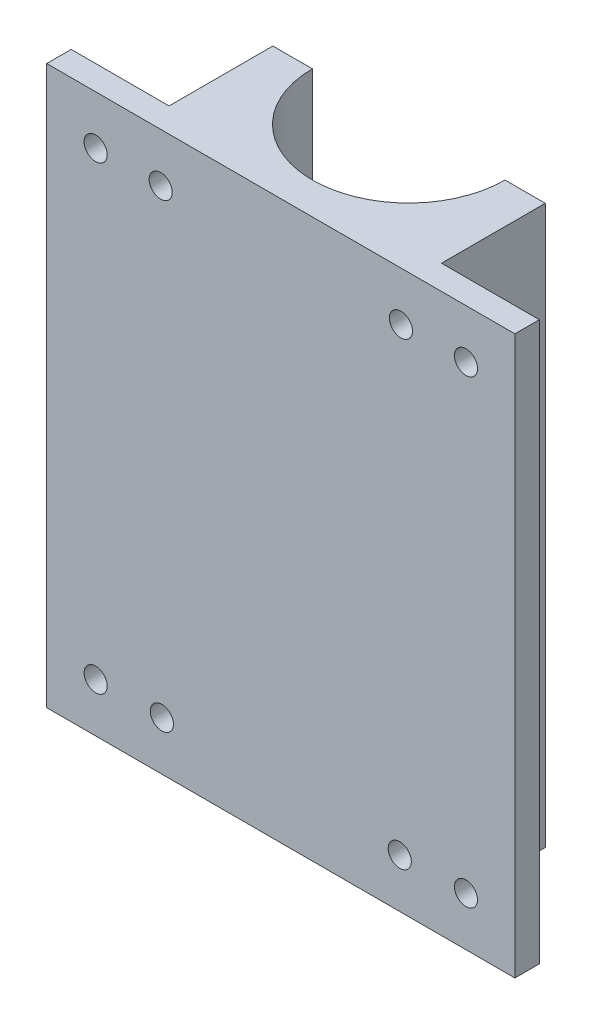
SolidWorks part; units mm, degrees
ref_plane "Front Plane" through (0, 0, 0) normal (0, 0, 1) x (1, 0, 0)
ref_plane "Top Plane" through (0, 0, 0) normal (0, 1, 0) x (1, 0, 0)
ref_plane "Right Plane" through (0, 0, 0) normal (1, 0, 0) x (0, 0, -1)
sketch "Sketch1" plane through (0, 0, 0) normal (0, 1, 0) x (1, 0, 0)
  line L1 (-23.8485, 17.6982) -> (36.9033, 17.6982)
  line L2 (-23.8485, 17.6982) -> (-23.8485, 14.5232)
  line L3 (-23.8485, 14.5232) -> (36.9033, 14.5232)
  line L4 (36.9033, 17.6982) -> (36.9033, 14.5232)
  line L6 (24.2033, 31.1659) -> (-11.1467, 31.1659)
  line L7 (24.2033, 31.1659) -> (24.2033, 17.6982)
  line L8 (24.2033, 17.6982) -> (-11.1467, 17.6982)
  line L9 (-11.1467, 31.1659) -> (-11.1467, 17.6982)
  line L10 (-6.0203, 31.1659) -> (-5.7203, 31.1659)
  line L11 (18.9797, 31.1659) -> (18.6797, 31.1659)
  line L12 (6.5283, 38.6577) -> (6.5283, -0.813) construction
  arc A2 (-6.0203, 31.1659) -> (18.9797, 31.1659) centre (6.4797, 31.1659) ccw
  arc A3 (-5.7203, 31.1659) -> (18.6797, 31.1659) centre (6.4797, 31.1659) ccw
  dimension "D1" = 12.7018
  dimension "D2" = 12.7
extrude "Boss-Extrude3" add sketch "Sketch1" along normal blind 72.39 contours A2 L6 L9 L1 | L12 A2 L1 L2 L3 | L1 L12 L3 L4 | A2 L1 L7 L6 region at (6.5274, 0, -16.1107) region at (-10.7684, 0, -24.432)
extrude "Boss-Extrude4" add sketch "Sketch1<13>" along normal blind 51.39 contours A2 L11 A3 L10
sketch "Sketch1<13>" plane through (0, 0, 0) normal (0, 1, 0) x (1, 0, 0) same geometry as "Sketch1"
hole_wizard "Ø3.0mm Dowel Hole1" positions "Sketch4" profile "Sketch5" hole size "Ø3.0" standard "ANSI Metric" end condition through all
sketch "Sketch4" plane through (0, 0, -17.6982) normal (0, 0, -1) x (-1, 0, 0)
  line L0 (-24.2033, 72.39) -> (-36.9033, 72.39) construction
  line L1 (-36.9033, 72.39) -> (-36.9033, 0) construction
  line L3 (-24.2033, 0) -> (-36.9033, 0) construction
  point P0 (-30.5533, 66.04)
  point P9 (-30.5533, 6.35)
  point P20 (-30.5533, 0)
  dimension "D1" = 6.35
  dimension "D2" = 6.35
  dimension "D3" = 6.35
  dimension "D4" = 6.35
sketch "Sketch5" plane through (30.5533, 66.04, -17.6982) normal (1, 0, 0) x (0, 1, 0)
  line L0 (0, 0) -> (0, 3.175)
  line L1 (0, 3.175) -> (1.5, 3.175)
  line L2 (1.5, 3.175) -> (1.5, 0)
  line L5 (1.5, 0) -> (0, 0)
  line L11 (0, -6.35) -> (0, 107.95) construction
  dimension "Thru Hole Dia." = 3
  dimension "Thru Hole Depth" = 3.175
hole_wizard "Ø3.0mm Dowel Hole2" positions "Sketch6" profile "Sketch7" hole size "Ø3.0" standard "ANSI Metric" end condition through all
sketch "Sketch6" plane through (0, 0, -17.6982) normal (0, 0, -1) x (-1, 0, 0)
  line L0 (23.8485, 72.39) -> (11.1467, 72.39) construction
  line L1 (23.8485, 72.39) -> (23.8485, 0) construction
  line L2 (23.8485, 0) -> (11.1467, 0) construction
  point P0 (17.4985, 6.35)
  point P2 (17.4985, 66.04)
  dimension "D1" = 6.35
  dimension "D2" = 6.35
  dimension "D3" = 6.35
  dimension "D4" = 6.35
sketch "Sketch7" plane through (-17.4985, 6.35, -17.6982) normal (1, 0, 0) x (0, 1, 0)
  line L0 (0, 0) -> (0, 3.175)
  line L1 (0, 3.175) -> (1.5, 3.175)
  line L2 (1.5, 3.175) -> (1.5, 0)
  line L5 (1.5, 0) -> (0, 0)
  line L11 (0, -6.35) -> (0, 107.95) construction
  dimension "Thru Hole Dia." = 3
  dimension "Thru Hole Depth" = 3.175
hole_wizard "Ø3.0mm Dowel Hole4" positions "Sketch10" profile "Sketch11" hole size "Ø3.0" standard "ANSI Metric" end condition through all
sketch "Sketch10" plane through (0, 0, -31.1659) normal (0, 0, -1) x (-1, 0, 0)
  line L2 (-42.513, 66.04) -> (28.1638, 66.04) construction
  line L4 (-43.5181, 6.35) -> (29.2845, 6.35) construction
  line L6 (-24.2033, 72.39) -> (-24.2033, 0) construction
  line L7 (11.1467, 72.39) -> (11.1467, 0) construction
  line L8 (-24.2033, 72.39) -> (-24.2033, 0) construction
  line L9 (11.1467, 72.39) -> (11.1467, 0) construction
  point P0 (-22.1133, 66.04)
  point P2 (9.0567, 66.04)
  point P4 (8.9067, 6.35)
  point P5 (-21.9633, 6.35)
  dimension "D1" = 2.24
  dimension "D2" = 2.24
  dimension "D3" = 2.09
  dimension "D4" = 2.09
sketch "Sketch11" plane through (22.1133, 66.04, -31.1659) normal (1, 0, 0) x (0, 1, 0)
  line L0 (0, 0) -> (0, 16.6428)
  line L1 (0, 16.6428) -> (1.5, 16.6428)
  line L2 (1.5, 16.6428) -> (1.5, 0)
  line L5 (1.5, 0) -> (0, 0)
  line L11 (0, -6.35) -> (0, 107.95) construction
  dimension "Thru Hole Dia." = 3
  dimension "Thru Hole Depth" = 16.6428
